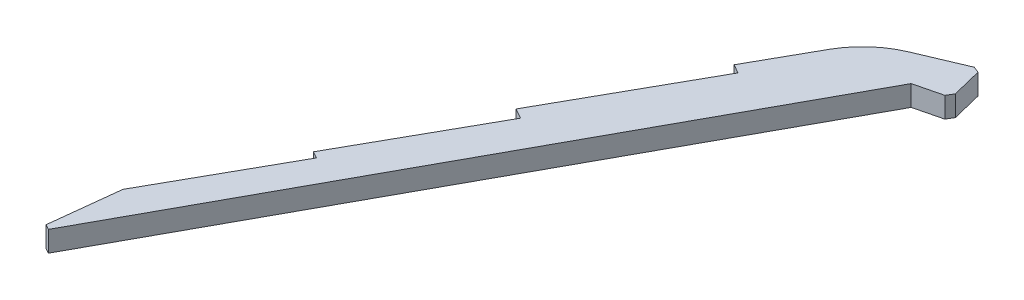
SolidWorks part; units mm, degrees
material "橡胶"
ref_plane "前视基准面" through (0, 0, 0) normal (0, 0, 1) x (1, 0, 0)
ref_plane "上视基准面" through (0, 0, 0) normal (0, 1, 0) x (1, 0, 0)
ref_plane "右视基准面" through (0, 0, 0) normal (1, 0, 0) x (0, 0, -1)
other "Configuration Table"
sketch "草图3" plane through (0, 0, 0) normal (0, 1, 0) x (1, 0, 0)
  line L0 (-187.956, -71.675) -> (-195.323, -74.7938) construction
  line L1 (-186.9991, -75.5588) -> (-187.956, -71.675) construction
  line L2 (-190.0225, -76.3037) -> (-186.9991, -75.5588) construction
  line L3 (-218.3204, -128.0228) -> (-190.0225, -76.3037) construction
  line L4 (-218.8019, -127.7593) -> (-218.3204, -128.0228) construction
  line L5 (-211.665, -109.5424) -> (-218.0237, -120.8812) construction
  line L6 (-218.0237, -120.8812) -> (-218.8019, -127.7593) construction
  line L7 (-199.0441, -83.3713) -> (-206.3811, -96.4545) construction
  line L8 (-195.323, -74.7938) -> (-199.8726, -82.9067) construction
  line L9 (-199.8726, -82.9067) -> (-199.0441, -83.3713) construction
  line L11 (-205.4417, -96.9813) -> (-206.3811, -96.4545) construction
  line L12 (-205.4417, -96.9813) -> (-212.2895, -109.1923) construction
  line L13 (-212.2895, -109.1923) -> (-211.665, -109.5424) construction
  line L36 (-187.1202, -75.4857) -> (-188.025, -71.8128)
  line L37 (-188.025, -71.8128) -> (-195.2525, -74.8725)
  line L38 (-195.2525, -74.8725) -> (-199.7365, -82.8684)
  line L39 (-199.7365, -82.8684) -> (-198.908, -83.333)
  line L40 (-198.908, -83.333) -> (-206.2449, -96.4162)
  line L41 (-206.2449, -96.4162) -> (-205.3055, -96.943)
  line L42 (-205.3055, -96.943) -> (-212.1533, -109.1539)
  line L43 (-212.1533, -109.1539) -> (-211.5289, -109.5041)
  line L44 (-211.5289, -109.5041) -> (-217.9266, -120.9125)
  line L45 (-217.9266, -120.9125) -> (-218.6464, -127.2744)
  line L46 (-218.6464, -127.2744) -> (-218.1681, -127.5361)
  line L47 (-218.1681, -127.5361) -> (-190.0891, -76.2171)
  line L99 (-190.0891, -76.2171) -> (-187.1202, -75.4857)
  dimension "D1" = 0.1
  dimension "D2" = 0.1
  dimension "D3" = 0.1
  dimension "D4" = 0.1
  dimension "D5" = 0.5
  dimension "D6" = 0.1
  dimension "D7" = 0.1
  dimension "D8" = 0.1
  dimension "D9" = 0.1
  dimension "D10" = 0.1
  dimension "D11" = 0.1
  dimension "D12" = 0.1
  dimension "D13" = 0.1
extrude "凸台-拉伸2" add sketch "草图3" along normal blind 0.95 and the other way blind 0.95
fillet "圆角6" radius 8 1 edges at (-195.2525, 0, 74.8725)
chamfer "倒角1" distance 0.5 angle 45 1 edges at (-187.1202, 0, 75.4857)
chamfer "倒角2" distance 0.5 angle 45 1 edges at (-188.025, 0, 71.8128) first distance on face at (-190.3786, 0, 72.8092)
